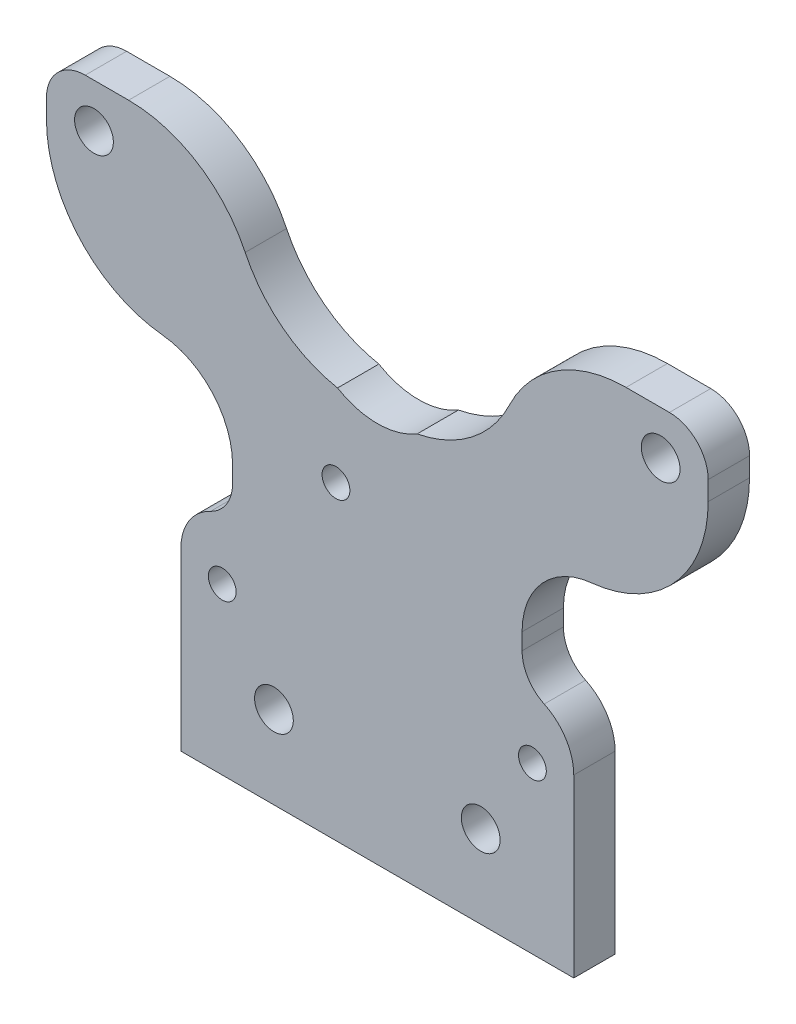
SolidWorks part; units mm, degrees
ref_plane "Front Plane" through (0, 0, 0) normal (0, 0, 1) x (1, 0, 0)
ref_plane "Top Plane" through (0, 0, 0) normal (0, 1, 0) x (1, 0, 0)
ref_plane "Right Plane" through (0, 0, 0) normal (1, 0, 0) x (0, 0, -1)
sketch "Sketch1" plane through (0, 0, 0) normal (0, 1, 0) x (1, 0, 0)
  line L1 (0, 0) -> (30.4, 0)
  line L2 (0, 0) -> (0, -3.2)
  line L3 (0, -3.2) -> (30.4, -3.2)
  line L4 (30.4, 0) -> (30.4, -3.2)
  dimension "D1" = 3.2
  dimension "D2" = 30.4
extrude "Boss-Extrude1" add sketch "Sketch1" along normal blind 17.6
sketch "Sketch2" plane through (0, 0, 3.2) normal (0, 0, 1) x (1, 0, 0)
  line L0 (30.4, 17.6) -> (30.4, 0) construction
  line L1 (0, 0) -> (30.4, 0) construction
  circle A0 centre (23.2, 6.4) radius 1.5
  circle A1 centre (7.2, 6.4) radius 1.5
  dimension "D5" = 3
  dimension "D6" = 3
  dimension "D1" = 7.2
  dimension "D2" = 6.4
  dimension "D3" = 6.4
  dimension "D4" = 16
extrude "Cut-Extrude1" cut sketch "Sketch2" against normal blind 16
sketch "Sketch3" plane through (0, 0, 0) normal (0, 0, -1) x (-1, 0, 0)
  line L0 (0, 17.6) -> (0, 0) construction
  line L1 (-30.4, 17.6) -> (0, 17.6) construction
  circle A0 centre (-27.2, 12.8) radius 1.075
  circle A1 centre (-3.2, 12.8) radius 1.075
  dimension "D2" = 2.15
  dimension "D3" = 2.15
  dimension "D1" = 24
  dimension "D4" = 3.2
  dimension "D5" = 4.8
  dimension "D6" = 4.8
extrude "Cut-Extrude2" cut sketch "Sketch3" against normal blind 16
sketch "Sketch4" plane through (0, 17.6, 0) normal (0, 1, 0) x (1, 0, 0)
  line L0 (0, -3.2) -> (30.4, -3.2) construction
  line L1 (4, -3.2) -> (26.4, -3.2)
  line L2 (4, -3.2) -> (4, 0)
  line L3 (4, 0) -> (26.4, 0)
  line L4 (26.4, -3.2) -> (26.4, 0)
  line L5 (30.4, 0) -> (0, 0) construction
extrude "Boss-Extrude2" add sketch "Sketch4" along normal blind 12.8
sketch "Sketch5" plane through (0, 0, 3.2) normal (0, 0, 1) x (1, 0, 0)
  line L1 (4, 30.4) -> (26.4, 30.4) construction
  line L2 (4, 30.4) -> (4, 17.6) construction
  circle A0 centre (12, 24) radius 1.075
  dimension "D2" = 6.4
  dimension "D1" = 2.15
  dimension "D3" = 8
extrude "Cut-Extrude3" cut sketch "Sketch5" against normal blind 16
sketch "Sketch6" plane through (0, 0, 3.2) normal (0, 0, 1) x (1, 0, 0)
  line L0 (4, 30.4) -> (4, 17.6) construction
  line L1 (4, 27.2) -> (-10.4, 27.2)
  line L2 (4, 27.2) -> (4, 41.6)
  line L3 (4, 41.6) -> (-10.4, 41.6)
  line L4 (-10.4, 27.2) -> (-10.4, 41.6)
  line L5 (4, 30.4) -> (26.4, 30.4) construction
  line L6 (15.2, 30.4) -> (15.2, 25.736) construction
  line L7 (26.4, 27.2) -> (26.4, 41.6)
  line L8 (26.4, 27.2) -> (40.8, 27.2)
  line L9 (40.8, 27.2) -> (40.8, 41.6)
  line L10 (26.4, 41.6) -> (40.8, 41.6)
  dimension "D1" = 3.2
  dimension "D2" = 14.4
  dimension "D3" = 14.4
extrude "Boss-Extrude3" add sketch "Sketch6" against normal blind 3.2
sketch "Sketch7" plane through (0, 0, 3.2) normal (0, 0, 1) x (1, 0, 0)
  line L0 (40.8, 27.2) -> (40.8, 41.6) construction
  line L4 (4, 41.6) -> (-10.4, 41.6) construction
  line L5 (40.8, 41.6) -> (26.4, 41.6) construction
  circle A0 centre (-6.725, 38.2) radius 1.5
  circle A1 centre (37.125, 38.2) radius 1.5
  dimension "D5" = 3
  dimension "D6" = 3
  dimension "D1" = 43.85
  dimension "D2" = 3.675
  dimension "D3" = 3.4
  dimension "D4" = 3.4
extrude "Cut-Extrude4" cut sketch "Sketch7" against normal through all
sketch "Sketch8" plane through (0, 0, 3.2) normal (0, 0, 1) x (1, 0, 0)
  circle A0 centre (15.2, 35.5498) radius 6
  dimension "D1" = 12
extrude "Cut-Extrude5" cut sketch "Sketch8" against normal blind 3.2
fillet "Fillet5" radius 4 2 edges at (0, 17.6, 1.6) (30.4, 17.6, 1.6)
fillet "Fillet6" radius 10 2 edges at (26.4, 30.4, 1.6) (4, 30.4, 1.6)
fillet "Fillet7" radius 6 2 edges at (26.4, 27.2, 1.6) (4, 27.2, 1.6)
fillet "Fillet8" radius 10 2 edges at (40.8, 27.2, 1.6) (-10.4, 27.2, 1.6)
fillet "Fillet9" radius 3 2 edges at (40.8, 41.6, 1.6) (-10.4, 41.6, 1.6)
fillet "Fillet10" radius 10 2 edges at (26.4, 41.6, 1.6) (4, 41.6, 1.6)
fillet "Fillet12" radius 3 2 edges at (4, 17.6, 1.6) (26.4, 17.6, 1.6)
equation "\"滑动-垂直孔\" = 0.6"
equation "\"滑动-水平孔\" = 0.3"
equation "\"松动-垂直孔\" = 0.3"
equation "\"松动-水平孔\" = 0.1"
equation "\"正常-垂直孔\" = 0.15"
equation "\"正常-水平孔\" = 0"
equation "\"紧缩-垂直孔\" = 0"
equation "\"紧缩-水平孔\" = -0.1"
equation "\"_喷嘴物理宽度\" = 0.8"
equation "\"_喷嘴宽度系数\" = 1"
equation "\"_物理厚度\" = 0.4"
equation "\"_物理厚度系数\" = 2"
equation "\"喷嘴宽度\" = \"_喷嘴物理宽度\" * \"_喷嘴宽度系数\""
equation "\"喷嘴厚度\" = \"_物理厚度\" * \"_物理厚度系数\""
equation "\"D1@Sketch1\"=\"喷嘴宽度\"*4"
equation "\"D2@Sketch1\"=\"喷嘴宽度\"*38"
equation "\"D1@Boss-Extrude1\"=\"喷嘴宽度\"*22"
equation "\"D1@Sketch2\"=\"喷嘴宽度\"*9"
equation "\"D2@Sketch2\"=\"喷嘴宽度\"*8"
equation "\"D3@Sketch2\"=\"D2@Sketch2\""
equation "\"D4@Sketch2\"=\"喷嘴厚度\"*20"
equation "\"D5@Sketch2\"=\"紧缩-垂直孔\"+3"
equation "\"D6@Sketch2\"=\"D5@Sketch2\""
equation "\"D2@Sketch3\"=\"正常-垂直孔\"+2"
equation "\"D3@Sketch3\"=\"D2@Sketch3\""
equation "\"D4@Sketch3\"=\"喷嘴宽度\"*4"
equation "\"D5@Sketch3\"=\"喷嘴宽度\"*6"
equation "\"D6@Sketch3\"=\"D5@Sketch3\""
equation "\"D1@Sketch4\"=\"喷嘴宽度\"*5"
equation "\"D2@Sketch4\"=\"D1@Sketch4\""
equation "\"D1@Boss-Extrude2\"=\"喷嘴宽度\"*16"
equation "\"D1@Sketch5\"=\"正常-垂直孔\"+2"
equation "\"D2@Sketch5\"=\"喷嘴宽度\"*8"
equation "\"D3@Sketch5\"=\"喷嘴宽度\"*10"
equation "\"D1@Sketch6\"=\"喷嘴宽度\"*4"
equation "\"D2@Sketch6\"=\"喷嘴宽度\"*18"
equation "\"D3@Sketch6\"=\"喷嘴宽度\"*18"
equation "\"D1@Boss-Extrude3\"=\"喷嘴宽度\"*4"
equation "\"D2@Sketch7\"=7.35/2"
equation "\"D3@Sketch7\"=\"喷嘴宽度\"*4.25"
equation "\"D4@Sketch7\"=\"D3@Sketch7\""
equation "\"D5@Sketch7\"=\"紧缩-垂直孔\"+3"
equation "\"D6@Sketch7\"=\"D5@Sketch7\""
